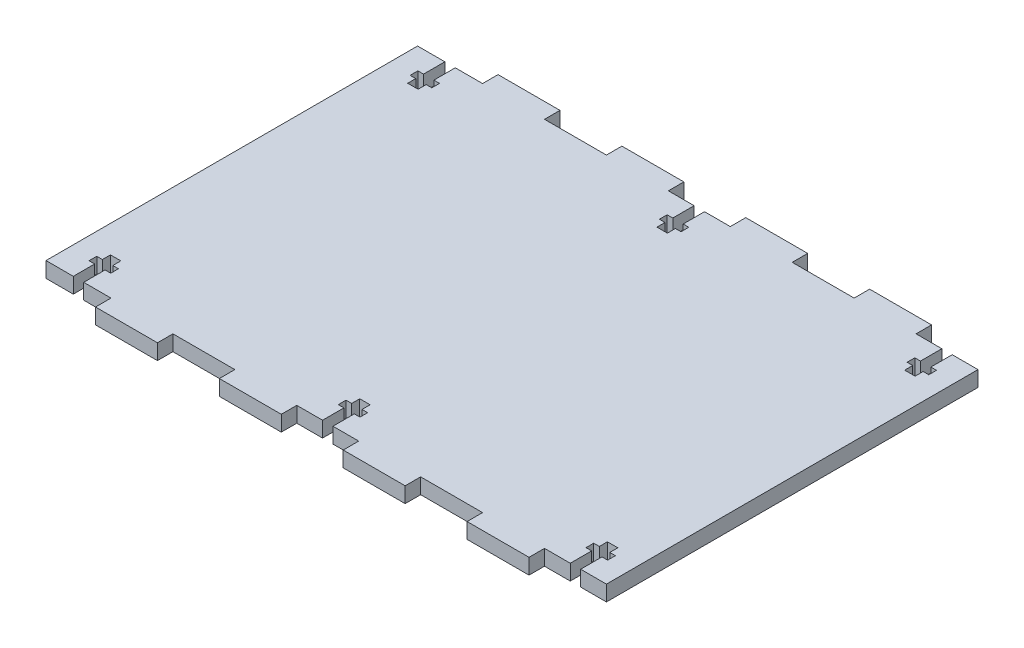
SolidWorks part; units mm, degrees
ref_plane "Front Plane" through (0, 0, 0) normal (0, 0, 1) x (1, 0, 0)
ref_plane "Top Plane" through (0, 0, 0) normal (0, 1, 0) x (1, 0, 0)
ref_plane "Right Plane" through (0, 0, 0) normal (1, 0, 0) x (0, 0, -1)
sketch "Sketch1" plane through (0, 0, 0) normal (0, 0, 1) x (1, 0, 0)
  line L0 (90.51, -15.875) -> (90.51, 155.575) construction
  line L1 (-139.3499, 155.575) -> (90.51, 155.575)
  line L2 (-139.3499, 155.575) -> (-139.3499, 149.225)
  line L3 (-139.3499, 149.225) -> (90.51, 149.225)
  line L4 (90.51, 155.575) -> (90.51, 149.225)
  dimension "D1" = 6.35
extrude "Boss-Extrude1" add sketch "Sketch1" along normal blind 152.4
sketch "Sketch2" plane through (0, 155.575, 0) normal (0, 1, 0) x (1, 0, 0)
  line L0 (65.11, 0) -> (65.11, 6.35)
  line L1 (90.51, 0) -> (-139.3499, 0) construction
  line L2 (-139.3499, 6.35) -> (-112.69, 6.35) construction
  line L3 (65.11, 6.35) -> (39.71, 6.35)
  line L4 (39.71, 6.35) -> (39.71, 0)
  line L5 (90.51, 0) -> (65.11, 0)
  line L6 (65.11, 0) -> (39.71, 0)
  line L9 (90.51, 0) -> (-139.3499, 0)
  line L10 (-139.3499, 0) -> (-139.3499, -152.4)
  line L11 (-139.3499, -152.4) -> (90.51, -152.4)
  line L12 (90.51, -152.4) -> (90.51, 0)
  line L13 (39.71, 0) -> (-139.3499, 0)
  line L14 (-139.3499, 0) -> (-139.3499, -152.4)
  line L15 (-139.3499, -152.4) -> (90.51, -152.4)
  line L16 (90.51, -152.4) -> (90.51, 0)
  line M7 (90.51, 0) -> (-139.3499, 0)
  dimension "D1" = 25.4
  dimension "D2" = 25.4
  dimension "D3" = 0
extrude "Boss-Extrude2" add sketch "Sketch2" against normal blind 6.35 contours L3 L4 L0 M7 region at (52.41, 155.575, -3.175)
pattern_linear "LPattern1" count 4 spacing 50.8 along (-1, 0, 0) of "Boss-Extrude2"
sketch "Sketch3" plane through (0, 0, 152.4) normal (0, 0, 1) x (1, 0, 0)
  line L0 (90.51, 155.575) -> (-139.3499, 155.575) construction
  line L1 (65.11, 155.575) -> (39.71, 155.575)
  line L2 (65.11, 155.575) -> (65.11, 149.225)
  line L3 (65.11, 149.225) -> (39.71, 149.225)
  line L4 (39.71, 155.575) -> (39.71, 149.225)
  line L5 (-139.3499, 149.225) -> (90.51, 149.225) construction
  dimension "D1" = 25.4
  dimension "D2" = 25.4
extrude "Boss-Extrude3" add sketch "Sketch3" along normal blind 6.35
pattern_linear "LPattern2" count 4 spacing 50.8 along (-1, 0, 0) of "Boss-Extrude3"
sketch "Sketch4" plane through (0, 155.575, 0) normal (0, 1, 0) x (1, 0, 0)
  line L0 (-139.3499, 0) -> (-112.69, 0) construction
  line L1 (65.11, 0) -> (90.51, 0) construction
  line L2 (-126.0199, 0) -> (-126.0199, -13.6148) construction
  line L3 (-112.69, 0) -> (-139.3499, 0) construction
  line L4 (-23.79, 0) -> (-23.79, -16.5479) construction
  line L5 (-11.09, 0) -> (-36.49, 0) construction
  line L6 (77.81, 0) -> (77.81, -21.5198) construction
  line L7 (90.51, 0) -> (65.11, 0) construction
  line L8 (77.81, -152.4) -> (77.81, -137.4626) construction
  line L9 (90.51, -152.4) -> (65.11, -152.4) construction
  line L10 (-23.79, -152.4) -> (-23.79, -137.4626) construction
  line L11 (-11.09, -152.4) -> (-36.49, -152.4) construction
  line L12 (-126.0199, -152.4) -> (-126.0199, -137.4626) construction
  line L13 (-112.69, -152.4) -> (-139.3499, -152.4) construction
  line L14 (-139.3499, -152.4) -> (-112.69, -152.4) construction
  line L15 (-36.49, -152.4) -> (-11.09, -152.4) construction
  line B0 (-123.8863, 0) -> (-128.1535, 0)
  line B1 (-128.1535, -11.938) -> (-130.4649, -11.938)
  line B2 (-130.4649, -11.938) -> (-130.4649, -8.763)
  line B3 (-130.4649, -8.763) -> (-128.1535, -8.763)
  line B4 (-128.1535, -8.763) -> (-128.1535, 0)
  line B5 (-128.1535, -11.938) -> (-128.1535, -15.24)
  line B6 (-128.1535, -15.24) -> (-123.8863, -15.24)
  line B7 (-123.8863, -11.938) -> (-123.8863, -15.24)
  line B8 (-123.8863, -8.763) -> (-123.8863, 0)
  line B9 (-121.5749, -8.763) -> (-123.8863, -8.763)
  line B10 (-121.5749, -11.938) -> (-121.5749, -8.763)
  line B11 (-123.8863, -11.938) -> (-121.5749, -11.938)
  line B12 (-21.6564, 0) -> (-25.9236, 0)
  line B13 (-25.9236, -11.938) -> (-28.235, -11.938)
  line B14 (-28.235, -11.938) -> (-28.235, -8.763)
  line B15 (-28.235, -8.763) -> (-25.9236, -8.763)
  line B16 (-25.9236, -8.763) -> (-25.9236, 0)
  line B17 (-25.9236, -11.938) -> (-25.9236, -15.24)
  line B18 (-25.9236, -15.24) -> (-21.6564, -15.24)
  line B19 (-21.6564, -11.938) -> (-21.6564, -15.24)
  line B20 (-21.6564, -8.763) -> (-21.6564, 0)
  line B21 (-19.345, -8.763) -> (-21.6564, -8.763)
  line B22 (-19.345, -11.938) -> (-19.345, -8.763)
  line B23 (-21.6564, -11.938) -> (-19.345, -11.938)
  line B24 (79.9436, 0) -> (75.6764, 0)
  line B25 (75.6764, -11.938) -> (73.365, -11.938)
  line B26 (73.365, -11.938) -> (73.365, -8.763)
  line B27 (73.365, -8.763) -> (75.6764, -8.763)
  line B28 (75.6764, -8.763) -> (75.6764, 0)
  line B29 (75.6764, -11.938) -> (75.6764, -15.24)
  line B30 (75.6764, -15.24) -> (79.9436, -15.24)
  line B31 (79.9436, -11.938) -> (79.9436, -15.24)
  line B32 (79.9436, -8.763) -> (79.9436, 0)
  line B33 (82.255, -8.763) -> (79.9436, -8.763)
  line B34 (82.255, -11.938) -> (82.255, -8.763)
  line B35 (79.9436, -11.938) -> (82.255, -11.938)
  line B36 (-128.1535, -152.4) -> (-123.8863, -152.4)
  line B37 (-123.8863, -140.462) -> (-121.5749, -140.462)
  line B38 (-121.5749, -140.462) -> (-121.5749, -143.637)
  line B39 (-121.5749, -143.637) -> (-123.8863, -143.637)
  line B40 (-123.8863, -143.637) -> (-123.8863, -152.4)
  line B41 (-123.8863, -140.462) -> (-123.8863, -137.16)
  line B42 (-123.8863, -137.16) -> (-128.1535, -137.16)
  line B43 (-128.1535, -140.462) -> (-128.1535, -137.16)
  line B44 (-128.1535, -143.637) -> (-128.1535, -152.4)
  line B45 (-130.4649, -143.637) -> (-128.1535, -143.637)
  line B46 (-130.4649, -140.462) -> (-130.4649, -143.637)
  line B47 (-128.1535, -140.462) -> (-130.4649, -140.462)
  line B48 (-25.9236, -152.4) -> (-21.6564, -152.4)
  line B49 (-21.6564, -140.462) -> (-19.345, -140.462)
  line B50 (-19.345, -140.462) -> (-19.345, -143.637)
  line B51 (-19.345, -143.637) -> (-21.6564, -143.637)
  line B52 (-21.6564, -143.637) -> (-21.6564, -152.4)
  line B53 (-21.6564, -140.462) -> (-21.6564, -137.16)
  line B54 (-21.6564, -137.16) -> (-25.9236, -137.16)
  line B55 (-25.9236, -140.462) -> (-25.9236, -137.16)
  line B56 (-25.9236, -143.637) -> (-25.9236, -152.4)
  line B57 (-28.235, -143.637) -> (-25.9236, -143.637)
  line B58 (-28.235, -140.462) -> (-28.235, -143.637)
  line B59 (-25.9236, -140.462) -> (-28.235, -140.462)
  line B60 (75.6764, -152.4) -> (79.9436, -152.4)
  line B61 (79.9436, -140.462) -> (82.255, -140.462)
  line B62 (82.255, -140.462) -> (82.255, -143.637)
  line B63 (82.255, -143.637) -> (79.9436, -143.637)
  line B64 (79.9436, -143.637) -> (79.9436, -152.4)
  line B65 (79.9436, -140.462) -> (79.9436, -137.16)
  line B66 (79.9436, -137.16) -> (75.6764, -137.16)
  line B67 (75.6764, -140.462) -> (75.6764, -137.16)
  line B68 (75.6764, -143.637) -> (75.6764, -152.4)
  line B69 (73.365, -143.637) -> (75.6764, -143.637)
  line B70 (73.365, -140.462) -> (73.365, -143.637)
  line B71 (75.6764, -140.462) -> (73.365, -140.462)
sketch_block_instance "TSlot-1"
sketch_block "TSlot" parameters "D1"=3.302, "D2"=3.175
sketch_block_instance "TSlot-3"
sketch_block_instance "TSlot-4"
sketch_block_instance "TSlot-9"
sketch_block_instance "TSlot-11"
sketch_block_instance "TSlot-12"
extrude "Cut-Extrude1" cut sketch "Sketch4" against normal blind 6.35
